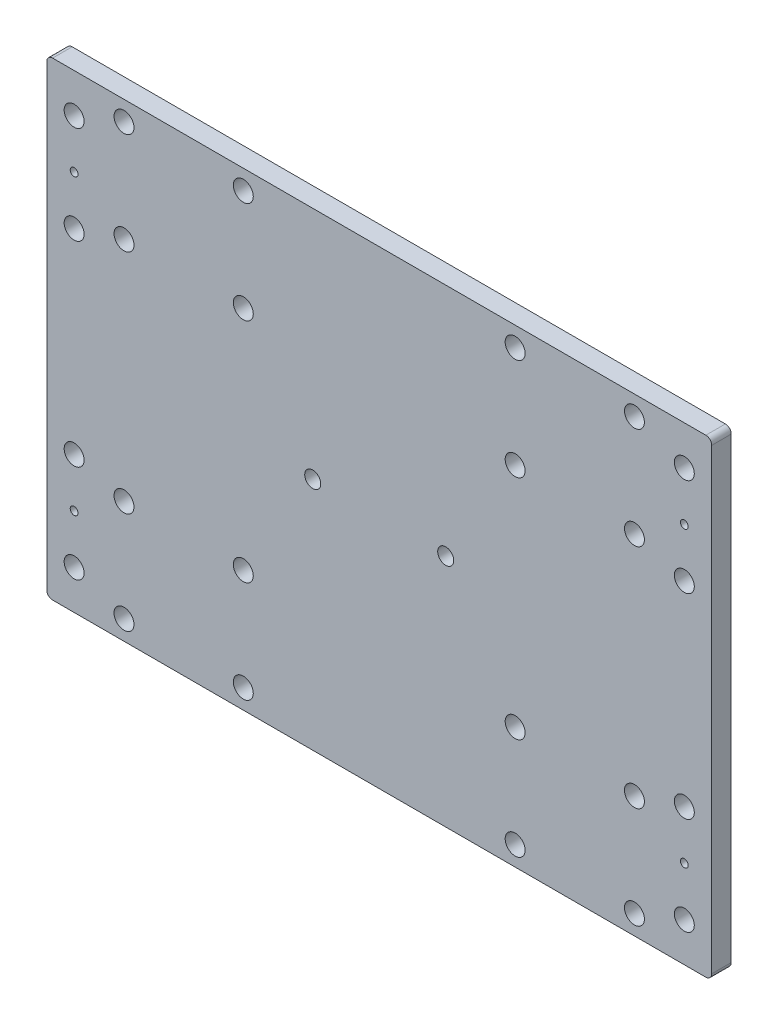
SolidWorks part; units mm, degrees
ref_plane "Front Plane" through (0, 0, 0) normal (0, 0, 1) x (1, 0, 0)
ref_plane "Top Plane" through (0, 0, 0) normal (0, 1, 0) x (1, 0, 0)
ref_plane "Right Plane" through (0, 0, 0) normal (1, 0, 0) x (0, 0, -1)
sketch "Sketch1" plane through (0, 0, 0) normal (0, 0, 1) x (1, 0, 0)
  line L1 (85, -60) -> (-85, -60)
  line L2 (85, -60) -> (85, 60)
  line L3 (85, 60) -> (-85, 60)
  line L4 (-85, -60) -> (-85, 60)
  line L5 (85, -60) -> (-85, 60) construction
  line L6 (85, 60) -> (-85, -60) construction
  point P0 (0, 0)
  dimension "D1" = 170
  dimension "D2" = 120
extrude "Boss-Extrude1" add sketch "Sketch1" along normal mid plane 5
sketch "Sketch2" plane through (0, 0, 2.5) normal (0, 0, 1) x (1, 0, 0)
  line L0 (-65.25, 71) -> (-65.25, -71) construction
  line L1 (65.25, -71) -> (65.25, 71) construction
  line L2 (-34.75, 71) -> (-34.75, -71) construction
  line L3 (34.75, -71) -> (34.75, 71) construction
  line L4 (70.6711, 55) -> (-71.3289, 55) construction
  line L5 (-71.3289, -55) -> (70.6711, -55) construction
  line L6 (70.6711, 29) -> (-71.3289, 29) construction
  line L7 (-71.3289, -29) -> (70.6711, -29) construction
  line L8 (85, 60) -> (-85, 60) construction
  line L9 (-85, -60) -> (85, -60) construction
  line L10 (-85, 60) -> (-85, -60) construction
  line L11 (85, -60) -> (85, 60) construction
  circle A0 centre (-65.25, 55) radius 2.55
  circle A1 centre (-34.75, 55) radius 2.55
  circle A2 centre (-34.75, 29) radius 2.55
  circle A3 centre (-65.25, 29) radius 2.55
  circle A4 centre (65.25, 55) radius 2.55
  circle A5 centre (65.25, 29) radius 2.55
  circle A6 centre (34.75, 29) radius 2.55
  circle A7 centre (34.75, 55) radius 2.55
  circle A8 centre (-65.25, -29) radius 2.55
  circle A9 centre (-34.75, -29) radius 2.55
  circle A10 centre (-34.75, -55) radius 2.55
  circle A11 centre (-65.25, -55) radius 2.55
  circle A12 centre (34.75, -29) radius 2.55
  circle A13 centre (65.25, -29) radius 2.55
  circle A14 centre (65.25, -55) radius 2.55
  circle A15 centre (34.75, -55) radius 2.55
  dimension "D1" = 5.1
  dimension "D2" = 5.1
  dimension "D3" = 5.1
  dimension "D4" = 5.1
  dimension "D5" = 5.1
  dimension "D6" = 5.1
  dimension "D7" = 5.1
  dimension "D8" = 5.1
  dimension "D9" = 5.1
  dimension "D10" = 5.1
  dimension "D11" = 5.1
  dimension "D12" = 5.1
  dimension "D13" = 5.1
  dimension "D14" = 5.1
  dimension "D15" = 5.1
  dimension "D16" = 5.1
  dimension "D17" = 5
  dimension "D18" = 5
  dimension "D19" = 26
  dimension "D20" = 26
  dimension "D21" = 30.5
  dimension "D22" = 30.5
  dimension "D23" = 19.75
  dimension "D24" = 19.75
extrude "Cut-Extrude1" cut sketch "Sketch2" against normal through all
sketch "Sketch4" plane through (0, 0, 2.5) normal (0, 0, 1) x (1, 0, 0)
  line L3 (-17, 0) -> (17, 0) construction
  circle A0 centre (-17, 0) radius 2.05
  circle A3 centre (17, 0) radius 2.05
  point P0 (0, 0)
  dimension "D3" = 4.1
  dimension "D4" = 4.1
  dimension "D1" = 34
extrude "Cut-Extrude3" cut sketch "Sketch4" against normal through all
fillet "Fillet1" radius 1.5 4 edges at (-85, -60, 0) (85, -60, 0) (85, 60, 0) (-85, 60, 0)
sketch "Sketch6" plane through (0, 0, 2.5) normal (0, 0, 1) x (1, 0, 0)
  line L0 (-78, -1002.1032) -> (-78, 48997.8968) construction
  line L1 (78, -1010.3548) -> (78, 48989.6452) construction
  line L2 (-85, 58.5) -> (-85, -58.5) construction
  line L3 (85, -58.5) -> (85, 58.5) construction
  line L4 (83.5, 60) -> (-83.5, 60) construction
  line L5 (-83.5, -60) -> (83.5, -60) construction
  circle A0 centre (-78, 50) radius 2.55
  circle A1 centre (-78, 37.5) radius 1
  circle A2 centre (-78, 25) radius 2.55
  circle A3 centre (-78, -25) radius 2.55
  circle A4 centre (-78, -37.5) radius 1
  circle A5 centre (-78, -50) radius 2.55
  dimension "D3" = 5.1
  dimension "D4" = 2
  dimension "D5" = 5.1
  dimension "D6" = 5.1
  dimension "D7" = 5.1
  dimension "D8" = 2
  dimension "D9" = 10
  dimension "D12" = 35
  dimension "D14" = 10
  dimension "D1" = 7
  dimension "D2" = 7
  dimension "D10" = 22.5
  dimension "D11" = 35
  dimension "D13" = 22.5
extrude "Cut-Extrude5" cut sketch "Sketch6" against normal through all
mirror "Mirror1" about plane through (0, 0, 0) normal (1, 0, 0) of "Cut-Extrude5"
equation "\"D23@Sketch2\"=5.75+14"
equation "\"D24@Sketch2\"=5.75+14"
equation "\"D4@Sketch4\"=\"D3@Sketch4\""
equation "\"D5@Sketch6\" = \"D3@Sketch6\""
equation "\"D6@Sketch6\" = \"D3@Sketch6\""
equation "\"D7@Sketch6\"=\"D3@Sketch6\""
